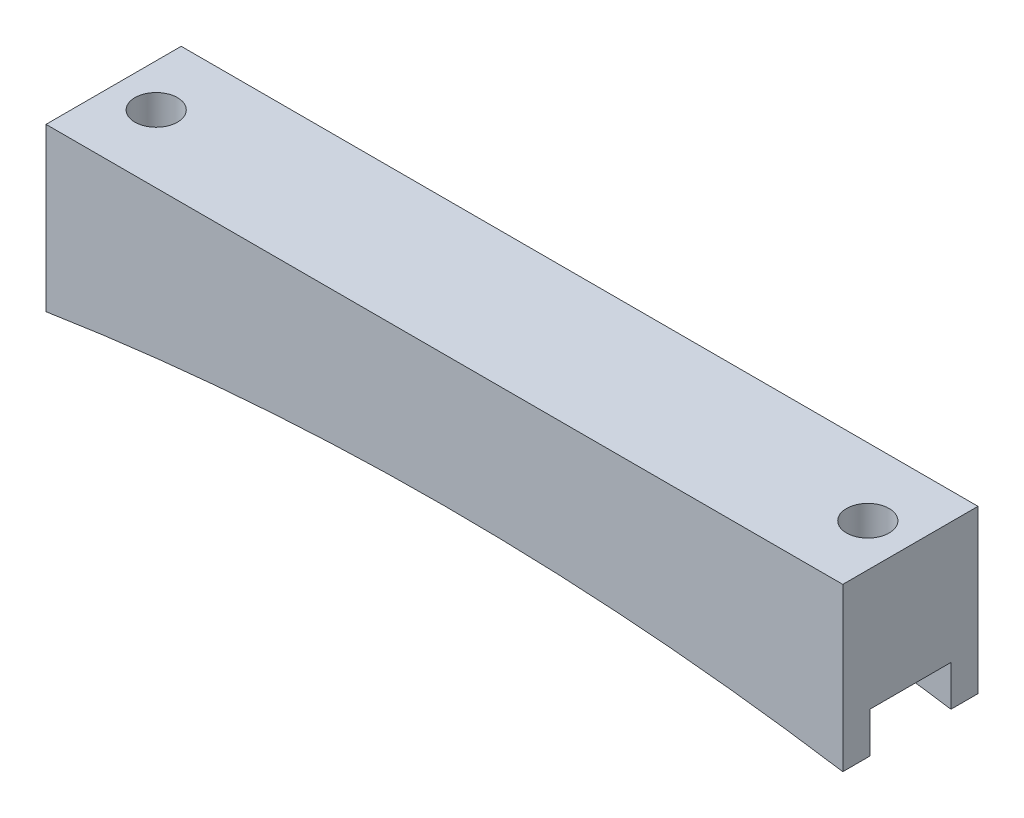
SolidWorks part; units mm, degrees
ref_plane "Front Plane" through (0, 0, 0) normal (0, 0, 1) x (1, 0, 0)
ref_plane "Top Plane" through (0, 0, 0) normal (0, 1, 0) x (1, 0, 0)
ref_plane "Right Plane" through (0, 0, 0) normal (1, 0, 0) x (0, 0, -1)
sketch "Sketch1" plane through (0, 0, 0) normal (0, 0, 1) x (1, 0, 0)
  line L0 (-37.4205, 0) -> (37.4205, 0)
  line L1 (-33.4205, -2.54) -> (33.4205, -2.54) construction
  line L2 (0, 0) -> (0, -4.6068) construction
  line L3 (37.4205, 0) -> (37.4205, -15.24)
  line L4 (-37.4205, 0) -> (-37.4205, -15.24)
  arc A0 (-37.4205, -15.24) -> (37.4205, -15.24) centre (0, -253.6208) cw
  point P4 (0, 0)
  point P9 (0, -2.54)
  dimension "D4" = 241.3
  dimension "D1" = 66.8409
  dimension "D2" = 2.54
  dimension "D3" = 4
  dimension "D5" = 15.24
extrude "Boss-Extrude1" add sketch "Sketch1" along normal blind 12.7
sketch "Sketch2" plane through (0, 0, 0) normal (0, 1, 0) x (1, 0, 0)
  line L1 (-33.4205, 0) -> (-33.4205, -12.7) construction
  line L2 (-37.4205, 0) -> (37.4205, 0) construction
  line L3 (37.4205, -12.7) -> (-37.4205, -12.7) construction
  line L4 (33.4205, 0) -> (33.4205, -12.7) construction
  circle A0 centre (-33.4205, -6.35) radius 2
  circle A1 centre (33.4205, -6.35) radius 2
  circle A2 centre (-33.4205, -6.35) radius 3 construction
  point P7 (-33.4205, -6.35)
  dimension "D1" = 4
  dimension "D2" = 6
extrude "Cut-Extrude1" cut sketch "Sketch2" against normal blind 6.5
sketch "Sketch3" plane through (37.4205, 0, 0) normal (1, 0, 0) x (0, 0, -1)
  line L0 (-12.7, -15.24) -> (0, -15.24) construction
  line L1 (-10.16, -15.24) -> (-2.54, -15.24)
  line L2 (-10.16, -15.24) -> (-10.16, -11.43)
  line L3 (-10.16, -11.43) -> (-2.54, -11.43)
  line L4 (-2.54, -15.24) -> (-2.54, -11.43)
  line L5 (-12.7, -15.24) -> (-12.7, 0) construction
  line L6 (0, -15.24) -> (0, 0) construction
  dimension "D1" = 2.54
  dimension "D2" = 2.54
  dimension "D3" = 3.81
extrude "Cut-Extrude2" cut sketch "Sketch3" against normal through all
